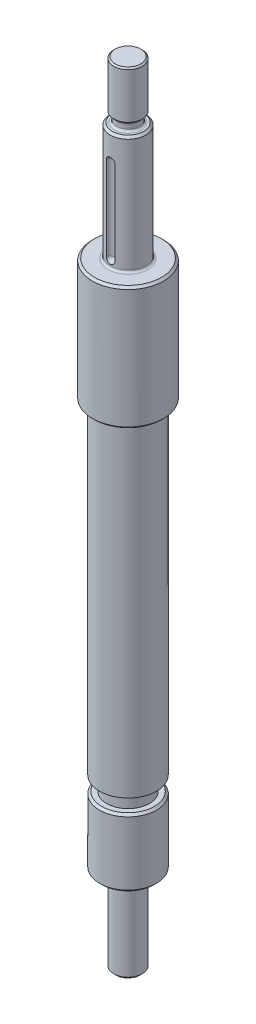
SolidWorks part; units mm, degrees
ref_plane "Front Plane" through (0, 0, 0) normal (0, 0, 1) x (1, 0, 0)
ref_plane "Top Plane" through (0, 0, 0) normal (0, 1, 0) x (1, 0, 0)
ref_plane "Right Plane" through (0, 0, 0) normal (1, 0, 0) x (0, 0, -1)
sketch "Sketch1" plane through (0, 0, 0) normal (0, 0, 1) x (1, 0, 0)
  line L0 (0, 0) -> (0, 119.1505) construction
  line L1 (0, 0) -> (2, 0)
  line L2 (2, 0) -> (2, 12)
  line L3 (2, 12) -> (4, 12)
  line L4 (4, 12) -> (4, 21.5)
  line L5 (4, 69) -> (5, 69)
  line L7 (5, 86.3) -> (2.5, 86.3)
  line L8 (2.5, 86.3) -> (2.5, 102.8)
  line L9 (2, 110.8) -> (0, 110.8)
  line L10 (2, 110.8) -> (2, 104)
  line L11 (1.6, 102.8) -> (2.5, 102.8)
  line L12 (0, 110.8) -> (0, 0)
  line L13 (5, 86.3) -> (5, 69)
  line L15 (2, 104) -> (1.6, 104)
  line L16 (1.6, 104) -> (1.6, 102.8)
  line L17 (4, 23.5) -> (4, 69)
  line L18 (4, 21.5) -> (3, 21.5)
  line L20 (4, 23.5) -> (3, 23.5)
  line L21 (3, 21.5) -> (3, 23.5)
  line L22 (0, 0) -> (0, -13.7807) construction
  point P20 (0, 119.1505)
  point P22 (0, -13.7807)
  dimension "D1" = 17.3
  dimension "D2" = 8
  dimension "D3" = 5
  dimension "D4" = 4
  dimension "D5" = 3.2
  dimension "D6" = 16.5
  dimension "D7" = 10
  dimension "D8" = 1.2
  dimension "D9" = 8
  dimension "D10" = 45.5
  dimension "D11" = 12
  dimension "D12" = 6
  dimension "D13" = 2
  dimension "D14" = 11.5
revolve "Revolve1" add sketch "Sketch1" angle 360 about L0
ref_plane "Plane2" through (0, 86.8, 0) normal (0, 1, 0) x (1, 0, 0)
sketch "Sketch2" plane through (0, 86.8, 0) normal (0, 1, 0) x (1, 0, 0)
  line L0 (0, 0) -> (6.8447, 0) construction
  circle A0 centre (0, 2.5) radius 0.6
  circle A1 centre (0, 0) radius 2.5 construction
  circle A2 centre (0, 0) radius 2.5 construction
  circle A3 centre (0, -2.5) radius 0.6
  point P11 (0.8677, 2.3446)
  dimension "D1" = 1.2
extrude "Cut-Extrude1" cut sketch "Sketch2" along normal offset from surface (13 mm away) 3 up to face at (0, 102.8, -1.6)
fillet "Fillet1" radius 0.6 4 edges at (0, 99.8, -1.9) (0, 86.8, -1.9) (0, 86.8, 1.9) (0, 99.8, 1.9)
chamfer "Chamfer1" distance 0.3 angle 45 2 edges at (0, 69, -5) (0, 86.3, -5)
chamfer "Chamfer2" distance 0.3 angle 45 2 edges at (0, 21.5, -4) (0, 12, -4)
chamfer "Chamfer3" distance 0.3 angle 45 1 edges at (0, 0, -2)
chamfer "Chamfer4" distance 0.3 angle 45 1 edges at (0, 102.8, -2.5)
chamfer "Chamfer5" distance 0.2 angle 45 2 edges at (0, 104, -2) (0, 110.8, -2)
fillet "Fillet2" radius 0.3 6 edges at (0, 23.5, -3) (0, 12, -2) (0, 69, -4) (0, 86.3, -2.5) (0, 104, -1.6) (0, 102.8, -1.6)
